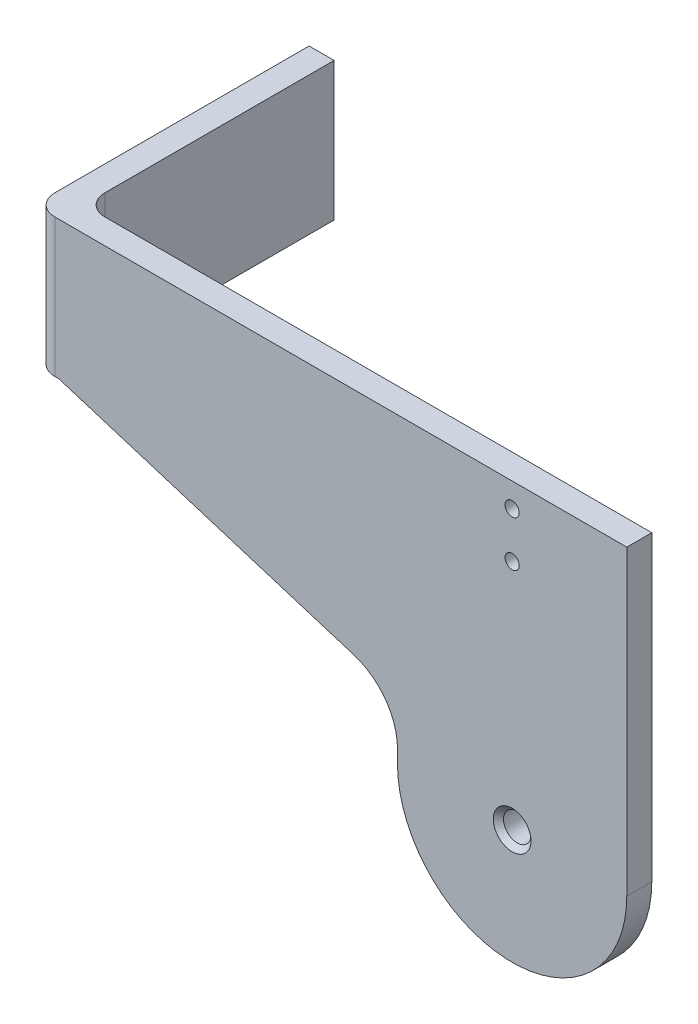
SolidWorks part; units mm, degrees
ref_plane "Piano frontale" through (0, 0, 0) normal (0, 0, 1) x (1, 0, 0)
ref_plane "Piano superiore" through (0, 0, 0) normal (0, 1, 0) x (1, 0, 0)
ref_plane "Piano destro" through (0, 0, 0) normal (1, 0, 0) x (0, 0, -1)
sketch "Schizzo2" plane through (0, 0, 0) normal (0, 0, 1) x (1, 0, 0)
  line L0 (0, 0) -> (0, 45) construction
  line L1 (-27.5, 0) -> (-27.5, 45)
  line L2 (27.5, 0) -> (27.5, 45)
  arc A0 (-27.5, 0) -> (27.5, 0) centre (0, 0) ccw
  arc A1 (27.5, 45) -> (-27.5, 45) centre (0, 45) ccw
  point P3 (0, 22.5)
  point P8 (0, -27.5)
  point P9 (0, 72.5)
  dimension "D1" = 100
  dimension "D2" = 55
extrude "Estrusione-Estrusione1" add sketch "Schizzo2" along normal blind 6
sketch "Schizzo3" plane through (0, 0, 0) normal (0, 0, 1) x (1, 0, 0)
  line L1 (27.5, 0) -> (-108.7, 0)
  line L2 (27.5, 0) -> (27.5, 72.5)
  line L3 (27.5, 72.5) -> (-108.7, 72.5)
  line L4 (-108.7, 0) -> (-108.7, 72.5)
  arc A0 (27.5, 45) -> (-27.5, 45) centre (0, 45) ccw construction
  point P9 (0, 72.5)
  dimension "D1" = 136.2
  dimension "D2" = 72.5
  dimension "D3" = 72.5
extrude "Estrusione-Estrusione2" add sketch "Schizzo3" along normal blind 6
sketch "Schizzo4" plane through (0, 0, 6) normal (0, 0, 1) x (1, 0, 0)
  line L2 (-27.5, 0) -> (-108.7, 0)
  line L3 (-108.7, 0) -> (-108.7, 39.3472)
  line L4 (-108.7, 39.3472) -> (-27.5, 14.1424)
  line L5 (-27.5, 14.1424) -> (-27.5, 0)
  line L6 (-108.7, 72.5) -> (-108.7, 0) construction
extrude "Taglio-Estrusione1" cut sketch "Schizzo4" against normal through all
fillet "Raccordo5" radius 15 1 edges at (-27.5, 14.1424, 3) type face fillet first side face at (-68.1, 26.7448, 3) second side face at (0, -13.75, 3) second side face at (-27.5, 7.0712, 3)
sketch "Schizzo9" plane through (0, 0, 0) normal (0, 0, 1) x (1, 0, 0)
  line L0 (-108.7, 39.3472) -> (-114.7, 39.3472)
  line L1 (-114.7, 39.3472) -> (-114.7, 72.5)
  line L2 (-114.7, 72.5) -> (-108.7, 72.5)
  line L3 (-108.7, 72.5) -> (-108.7, 39.3472)
extrude "Estrusione-Estrusione5" add sketch "Schizzo9" against normal blind 60 and the other way up to vertex (6 mm away) other way up to point (-108.7, 72.5, 6)
fillet "Raccordo6" radius 5 1 edges at (-108.7, 55.9236, 0) type face fillet first side face at (-36.1571, 25.5845, 0) second side face at (-108.7, 55.9236, -30)
fillet "Raccordo7" radius 5 1 edges at (-114.7, 55.9236, 6)
sketch "Schizzo10" plane through (0, 0, 0) normal (0, 0, -1) x (-1, 0, 0)
  line L0 (0, 72.5) -> (0, 66.71) construction
  line L1 (-27.5, 72.5) -> (103.7, 72.5) construction
  line L2 (0, 66.71) -> (0, 55.76) construction
  dimension "D1" = 5.79
  dimension "D2" = 10.95
hole_wizard "Foro lamato per Bullone M3 a testa esagonale-1" positions "Schizzo11" profile "Schizzo12" counterbore size "M3" standard "GB" end condition through all
sketch "Schizzo11" plane through (0, 0, 0) normal (0, 0, -1) x (-1, 0, 0)
  point P0 (0, 66.71)
  point P3 (0, 55.76)
sketch "Schizzo12" plane through (0, 66.71, 0) normal (1, 0, 0) x (0, 1, 0)
  line L0 (0, 0) -> (0, 6)
  line L1 (0, 6) -> (1.7, 6)
  line L3 (1.7, 6) -> (1.7, 0.5)
  line L4 (4.5, 0.5) -> (1.7, 0.5)
  line L5 (4.5, 0.5) -> (4.5, 0.025)
  line L6 (4.5, 0.025) -> (4.525, 0)
  line L7 (4.525, 0) -> (0, 0)
  line L8 (-4.5, 0.025) -> (-4.525, 0) construction
  line L11 (0, -6.35) -> (0, 107.95) construction
  dimension "Thru Hole Dia." = 3.4
  dimension "Thru Hole Depth" = 6
  dimension "C'Bore Dia." = 9
  dimension "C'Bore Depth" = 0.5
  dimension "Near C'Sink Dia." = 9.05
  dimension "Near C'Sink Angle" = 90
hole_wizard "Foro filettato G1/16-1" positions "Schizzo15" profile "Schizzo16" tap size "G1/16" standard "GB" end condition through all
sketch "Schizzo15" plane through (0, 0, 6) normal (0, 0, 1) x (1, 0, 0)
  point P0 (0, 0)
sketch "Schizzo16" plane through (0, 0, 6) normal (1, 0, 0) x (0, -1, 0)
  line L0 (0, 0) -> (0, 66)
  line L1 (0, 66) -> (3.3, 66)
  line L2 (3.3, 66) -> (3.3, 1.225)
  line L3 (3.3, 1.225) -> (4.525, 0)
  line L5 (4.525, 0) -> (0, 0)
  line L6 (-3.3, 1.225) -> (-4.525, 0) construction
  line L11 (0, -6.35) -> (0, 107.95) construction
  dimension "Thru Tap Drill Dia." = 6.6
  dimension "Thru Tap Drill Depth" = 66
  dimension "Near C'Sink Dia." = 9.05
  dimension "Near C'Sink Angle" = 90
cosmetic thread "Filettatura del foro1" parameters "D2"=7.723
